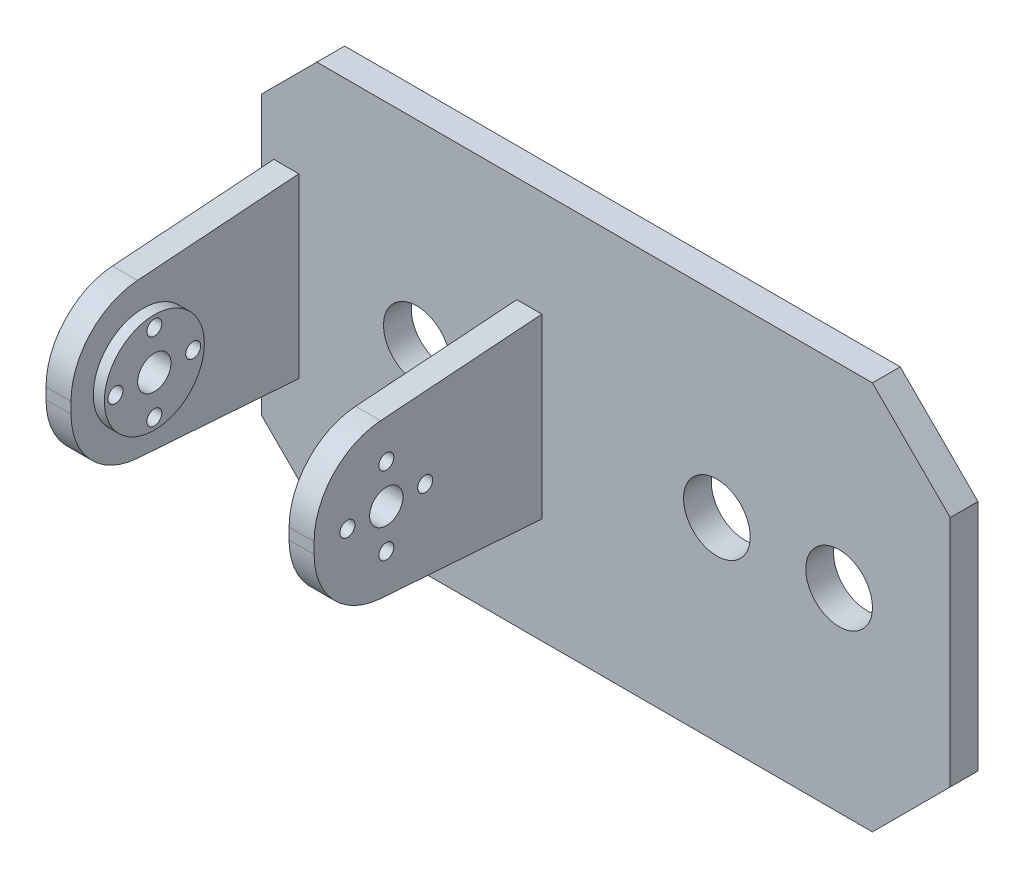
SolidWorks part; units mm, degrees
ref_plane "Front Plane" through (0, 0, 0) normal (0, 0, 1) x (1, 0, 0)
ref_plane "Top Plane" through (0, 0, 0) normal (0, 1, 0) x (1, 0, 0)
ref_plane "Right Plane" through (0, 0, 0) normal (1, 0, 0) x (0, 0, -1)
ref_plane "PZ_m33_000" through (0, 0, -33) normal (0, 0, 1) x (1, 0, 0)
sketch "S_prism1" plane through (0, 0, -33) normal (0, 0, 1) x (1, 0, 0)
  line L0 (56, -21) -> (56, 21)
  line L1 (56, 21) -> (42, 35)
  line L2 (42, 35) -> (-58, 35)
  line L3 (-58, 35) -> (-68, 25)
  line L4 (-68, 25) -> (-68, -25)
  line L5 (-68, -25) -> (-58, -35)
  line L6 (-58, -35) -> (42, -35)
  line L7 (42, -35) -> (56, -21)
extrude "Boss_1" add sketch "S_prism1" along normal blind 5
ref_plane "PX_m22_000" through (-22, 0, 0) normal (1, 0, 0) x (0, 0, -1)
sketch "S_prism2" plane through (-22, 0, 0) normal (1, 0, 0) x (0, 0, -1)
  line L0 (28.5, -16) -> (28.5, 16)
  line L1 (28.5, 16) -> (-1.0301, 13.8653)
  line L2 (-13, 0.9989) -> (-13, -0.9989)
  line L3 (-1.0301, -13.8653) -> (28.5, -16)
  arc A0 (-1.0301, 13.8653) -> (-13, 0.9989) centre (-0.1001, 0.999) ccw
  arc A1 (-13, -0.9989) -> (-1.0301, -13.8653) centre (-0.1001, -0.999) ccw
extrude "Boss_2" add sketch "S_prism2" along normal blind 4.5
ref_plane "PX_m61_250" through (-61.25, 0, 0) normal (1, 0, 0) x (0, 0, -1)
sketch "S_cyl3" plane through (-61.25, 0, 0) normal (1, 0, 0) x (0, 0, -1)
  circle A0 centre (0, 0) radius 9
  dimension "D1_S_cyl3" = 18
extrude "Boss_3" add sketch "S_cyl3" along normal blind 2
ref_plane "PX_m65_750" through (-65.75, 0, 0) normal (1, 0, 0) x (0, 0, -1)
sketch "S_prism4" plane through (-65.75, 0, 0) normal (1, 0, 0) x (0, 0, -1)
  line L0 (28.5, -16) -> (28.5, 16)
  line L1 (28.5, 16) -> (-1.0301, 13.8653)
  line L2 (-13, 0.9989) -> (-13, -0.9989)
  line L3 (-1.0301, -13.8653) -> (28.5, -16)
  arc A0 (-1.0301, 13.8653) -> (-13, 0.9989) centre (-0.1001, 0.999) ccw
  arc A1 (-13, -0.9989) -> (-1.0301, -13.8653) centre (-0.1001, -0.999) ccw
extrude "Boss_4" add sketch "S_prism4" along normal blind 4.5
ref_plane "PX_m22_100" through (-22.1, 0, 0) normal (1, 0, 0) x (0, 0, -1)
sketch "S_hole5" plane through (-22.1, 0, 0) normal (1, 0, 0) x (0, 0, -1)
  circle A0 centre (0, 0) radius 3
  dimension "D1_S_hole5" = 6
extrude "Hole_5" cut sketch "S_hole5" along normal blind 4.7
sketch "S_hole6" plane through (-22.1, 0, 0) normal (1, 0, 0) x (0, 0, -1)
  circle A0 centre (0, 7) radius 1.35
  dimension "D1_S_hole6" = 2.7
  dimension "P2" = 7
extrude "Hole_6" cut sketch "S_hole6" along normal blind 4.7
sketch "S_hole7" plane through (-22.1, 0, 0) normal (1, 0, 0) x (0, 0, -1)
  circle A0 centre (-7, 0) radius 1.35
  dimension "D1_S_hole7" = 2.7
  dimension "P2" = 7
extrude "Hole_7" cut sketch "S_hole7" along normal blind 4.7
sketch "S_hole8" plane through (-22.1, 0, 0) normal (1, 0, 0) x (0, 0, -1)
  circle A0 centre (0, -7) radius 1.35
  dimension "D1_S_hole8" = 2.7
  dimension "P2" = 7
extrude "Hole_8" cut sketch "S_hole8" along normal blind 4.7
sketch "S_hole9" plane through (-22.1, 0, 0) normal (1, 0, 0) x (0, 0, -1)
  circle A0 centre (7, 0) radius 1.35
  dimension "D1_S_hole9" = 2.7
  dimension "P2" = 7
extrude "Hole_9" cut sketch "S_hole9" along normal blind 4.7
ref_plane "PX_m65_850" through (-65.85, 0, 0) normal (1, 0, 0) x (0, 0, -1)
sketch "S_hole10" plane through (-65.85, 0, 0) normal (1, 0, 0) x (0, 0, -1)
  circle A0 centre (0, 0) radius 3
  dimension "D1_S_hole10" = 6
extrude "Hole_10" cut sketch "S_hole10" along normal blind 6.7
sketch "S_hole11" plane through (-65.85, 0, 0) normal (1, 0, 0) x (0, 0, -1)
  circle A0 centre (0, 7) radius 1.35
  dimension "D1_S_hole11" = 2.7
  dimension "P2" = 7
extrude "Hole_11" cut sketch "S_hole11" along normal blind 6.7
sketch "S_hole12" plane through (-65.85, 0, 0) normal (1, 0, 0) x (0, 0, -1)
  circle A0 centre (-7, 0) radius 1.35
  dimension "D1_S_hole12" = 2.7
  dimension "P2" = 7
extrude "Hole_12" cut sketch "S_hole12" along normal blind 6.7
sketch "S_hole13" plane through (-65.85, 0, 0) normal (1, 0, 0) x (0, 0, -1)
  circle A0 centre (0, -7) radius 1.35
  dimension "D1_S_hole13" = 2.7
  dimension "P2" = 7
extrude "Hole_13" cut sketch "S_hole13" along normal blind 6.7
sketch "S_hole14" plane through (-65.85, 0, 0) normal (1, 0, 0) x (0, 0, -1)
  circle A0 centre (7, 0) radius 1.35
  dimension "D1_S_hole14" = 2.7
  dimension "P2" = 7
extrude "Hole_14" cut sketch "S_hole14" along normal blind 6.7
ref_plane "PZ_m33_100" through (0, 0, -33.1) normal (0, 0, 1) x (1, 0, 0)
sketch "S_hole15" plane through (0, 0, -33.1) normal (0, 0, 1) x (1, 0, 0)
  circle A0 centre (-40, 0) radius 6
  dimension "D1_S_hole15" = 12
  dimension "P2" = 40
extrude "Hole_15" cut sketch "S_hole15" along normal blind 5.2
sketch "S_hole16" plane through (0, 0, -33.1) normal (0, 0, 1) x (1, 0, 0)
  circle A0 centre (14, 0) radius 6
  dimension "D1_S_hole16" = 12
  dimension "P2" = 14
extrude "Hole_16" cut sketch "S_hole16" along normal blind 5.2
sketch "S_hole17" plane through (0, 0, -33.1) normal (0, 0, 1) x (1, 0, 0)
  circle A0 centre (36, 0) radius 6
  dimension "D1_S_hole17" = 12
  dimension "P2" = 36
extrude "Hole_17" cut sketch "S_hole17" along normal blind 5.2
equation "\"plate_t\" = 3"
equation "\"clearance\" = 0.4"
